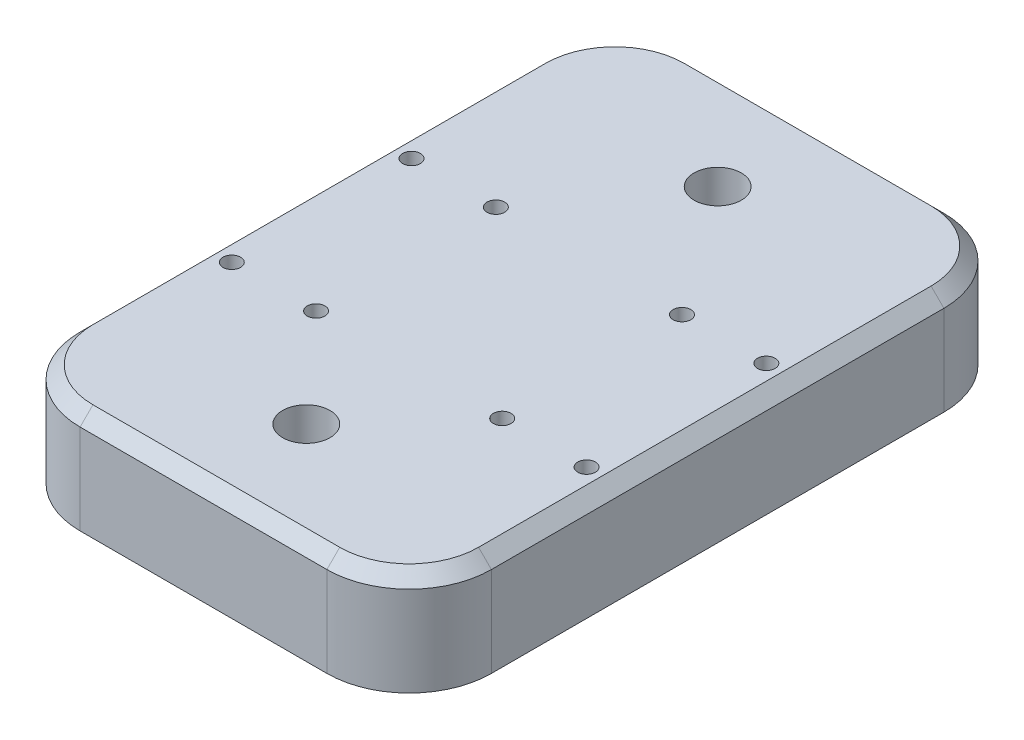
SolidWorks part; units mm, degrees
ref_plane "Front Plane" through (0, 0, 0) normal (0, 0, 1) x (1, 0, 0)
ref_plane "Top Plane" through (0, 0, 0) normal (0, 1, 0) x (1, 0, 0)
ref_plane "Right Plane" through (0, 0, 0) normal (1, 0, 0) x (0, 0, -1)
sketch "Sketch1" plane through (0, 0, 0) normal (1, 0, 0) x (0, 0, -1)
  line L3 (0, 12.7) -> (76.2, 12.7)
  line L4 (76.2, 12.7) -> (76.2, 0)
  line L5 (76.2, 0) -> (0, 0)
  line L6 (0, 12.7) -> (0, 0)
  dimension "D1" = 12.7
  dimension "D3" = 76.2
extrude "Boss-Extrude1" add sketch "Sketch1" along normal blind 50.8
sketch "Sketch3" plane through (0, 0, 0) normal (0, -1, 0) x (1, 0, 0)
  line L0 (50.8, 0) -> (0, 0) construction
  line L1 (25.4, -76.2) -> (25.4, 0) construction
  line L2 (50.8, -76.2) -> (0, -76.2) construction
  line L4 (0, -76.2) -> (0, 0) construction
  line L5 (50.8, -76.2) -> (0, -76.2) construction
  circle A1 centre (13.9065, -25.4) radius 1.0922
  circle A3 centre (25.4, -63.5) radius 2.921
  circle A4 centre (25.4, -12.7) radius 2.921
  circle A5 centre (3.4925, -25.4) radius 1.0922
  circle A6 centre (3.4925, -47.5996) radius 1.0922
  circle A7 centre (13.9065, -47.5996) radius 1.0922
  circle A8 centre (47.3075, -25.4) radius 1.0922
  circle A9 centre (36.8935, -25.4) radius 1.0922
  circle A10 centre (36.8935, -47.5996) radius 1.0922
  circle A11 centre (47.3075, -47.5996) radius 1.0922
  dimension "D1" = 2.1844
  dimension "D6" = 5.842
  dimension "D2" = 3.4925
  dimension "D3" = 22.1996
  dimension "D4" = 25.4
  dimension "D5" = 10.414
  dimension "D7" = 50.8
  dimension "D8" = 12.7
extrude "Cut-Extrude2" cut sketch "Sketch3" against normal through all
fillet "Fillet1" radius 10.16 4 edges at (0, 6.35, 0) (50.8, 6.35, 0) (0, 6.35, -76.2) (50.8, 6.35, -76.2)
chamfer "Chamfer1" distance 1.5875 angle 45 8 edges at (0, 12.7, -38.1) (2.9758, 12.7, -2.9758) (25.4, 12.7, 0) (47.8242, 12.7, -2.9758) (50.8, 12.7, -38.1) (47.8242, 12.7, -73.2242) (25.4, 12.7, -76.2) (2.9758, 12.7, -73.2242)
